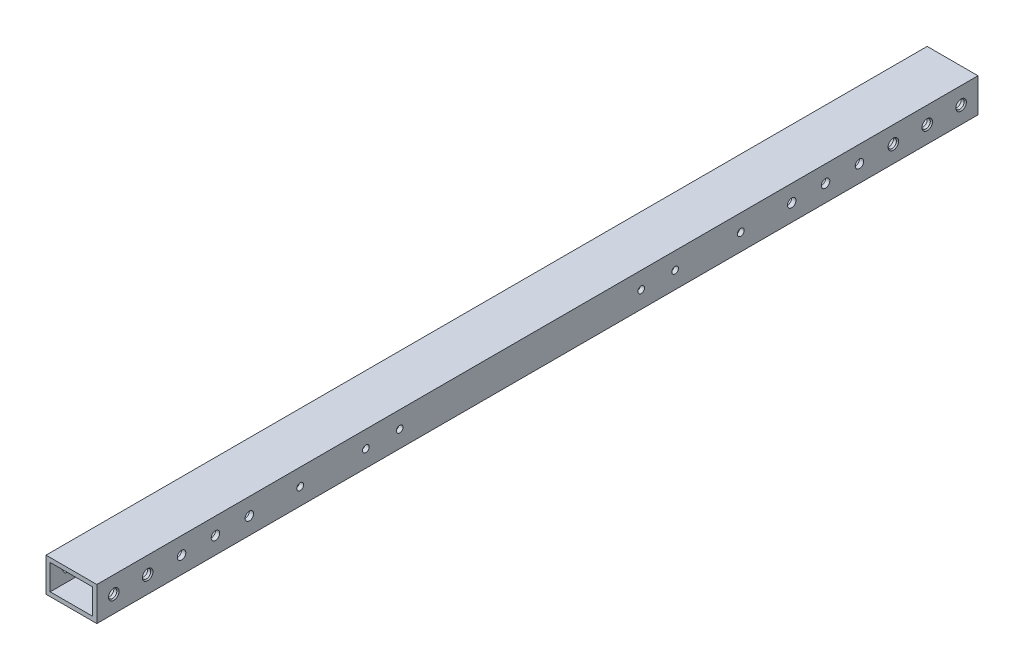
SolidWorks part; units mm, degrees
ref_plane "Front Plane" through (0, 0, 0) normal (0, 0, 1) x (1, 0, 0)
ref_plane "Top Plane" through (0, 0, 0) normal (0, 1, 0) x (1, 0, 0)
ref_plane "Right Plane" through (0, 0, 0) normal (1, 0, 0) x (0, 0, -1)
sketch "Sketch1" plane through (0, 0, 0) normal (0, 0, 1) x (1, 0, 0)
  line L0 (-15.875, 9.525) -> (15.875, 9.525)
  line L2 (-19.05, 12.7) -> (19.05, 12.7)
  line L3 (-19.05, 12.7) -> (-19.05, -12.7)
  line L4 (-19.05, -12.7) -> (19.05, -12.7)
  line L5 (19.05, 12.7) -> (19.05, -12.7)
  line L10 (15.875, 9.525) -> (15.875, -9.525)
  line L11 (-15.875, -9.525) -> (15.875, -9.525)
  line L12 (-15.875, 9.525) -> (-15.875, -9.525)
  point P12 (0, 12.7)
  point P14 (19.05, 0)
  dimension "Wall Thickness" = 3.175
  dimension "Outside Width" = 38.1
  dimension "Outside Height" = 25.4
  dimension "Inside Height" = 19.05
  dimension "Inside Width" = 31.75
sketch "Sketch2" plane through (0, 0, 0) normal (1, 0, 0) x (0, 0, -1)
  line L0 (330.2, 0) -> (-330.2, 0)
  point P4 (0, 0)
  point P7 (-330.2, 0)
  point P10 (330.2, 0)
  dimension "Length" = 660.4
sketch "Sketch3" plane through (0, 0, 0) normal (0, 0, 1) x (1, 0, 0)
  line L21 (19.05, 12.7) -> (-19.05, 12.7)
  line L22 (19.05, -12.7) -> (19.05, 12.7)
  line L23 (-19.05, -12.7) -> (19.05, -12.7)
  line L24 (-19.05, 12.7) -> (-19.05, -12.7)
  line L25 (19.05, 12.7) -> (-19.05, 12.7)
  line L26 (19.05, -12.7) -> (19.05, 12.7)
  line L27 (-19.05, -12.7) -> (19.05, -12.7)
  line L28 (-19.05, 12.7) -> (-19.05, -12.7)
  line L29 (15.875, 9.525) -> (-15.875, 9.525)
  line L30 (15.875, -9.525) -> (15.875, 9.525)
  line L31 (-15.875, -9.525) -> (15.875, -9.525)
  line L32 (-15.875, 9.525) -> (-15.875, -9.525)
  line L33 (15.875, 9.525) -> (-15.875, 9.525)
  line L34 (15.875, -9.525) -> (15.875, 9.525)
  line L35 (-15.875, -9.525) -> (15.875, -9.525)
  line L36 (-15.875, 9.525) -> (-15.875, -9.525)
  dimension "D1" = 0
  dimension "D2" = 0
extrude "Boss-Extrude1" add sketch "Sketch3" along normal up to vertex (330.2 mm away) and the other way up to vertex (330.2 mm away) up to point (0, 0, 330.2) other way up to point (0, 0, -330.2)
sketch "Drawing Reference" plane through (0, 0, 0) normal (1, 0, 0) x (0, 0, -1)
  line L0 (-330.2, 0) -> (330.2, 0) construction
  line L1 (0, -12.7) -> (0, 12.7) construction
  line L2 (-330.2, -12.7) -> (330.2, -12.7) construction
  line L5 (-330.2, 12.7) -> (330.2, 12.7) construction
  point P7 (-302.768, 0)
  point P8 (302.768, 0)
  dimension "D1" = 27.432
sketch "Sketch4" plane through (-19.05, 0, 0) normal (-1, 0, 0) x (0, 0, 1)
  line L0 (-330.2, 0) -> (-317.5574, 0)
  line L1 (-330.2, 12.7) -> (-330.2, -12.7) construction
  line L2 (-317.5574, 0) -> (-292.1574, 0)
  line L3 (-292.1574, 0) -> (-266.7574, 0)
  line L4 (-266.7574, 0) -> (-241.3574, 0)
  line L5 (-241.3574, 0) -> (-215.9574, 0)
  line L6 (-215.9574, 0) -> (-190.5574, 0)
  line L7 (330.2, 0) -> (317.5, 0)
  line L8 (330.2, 12.7) -> (330.2, -12.7) construction
  line L9 (317.5, 0) -> (292.1, 0)
  line L10 (292.1, 0) -> (266.7, 0)
  line L11 (266.7, 0) -> (241.3, 0)
  line L12 (241.3, 0) -> (215.9, 0)
hole_wizard "1/4 (0.25) Diameter Hole2" positions "Sketch7" profile "Sketch8" hole size "1/4" standard "ANSI Inch" end condition through all
sketch "Sketch7" plane through (-19.05, 0, 0) normal (-1, 0, 0) x (0, 0, 1)
  point P0 (-317.5574, 0)
  point P3 (-292.1574, 0)
  point P7 (317.5, 0)
  point P11 (-266.7574, 0)
  point P14 (292.1, 0)
sketch "Sketch8" plane through (-19.05, 0, -317.5574) normal (0, 1, 0) x (0, 0, 1)
  line L0 (0, 0) -> (0, 38.1)
  line L1 (0, 38.1) -> (3.9624, 38.1)
  line L2 (3.175, 37.1942) -> (3.175, 0)
  line L5 (3.175, 0) -> (0, 0)
  line L7 (3.9624, 38.1) -> (3.175, 37.1942)
  line L8 (-3.9624, 38.1) -> (-3.175, 37.1942) construction
  line L11 (0, -6.35) -> (0, 107.95) construction
  dimension "Thru Hole Dia." = 6.35
  dimension "Thru Hole Depth" = 38.1
  dimension "Far C'Sink Dia." = 7.9248
  dimension "Far C'Sink Angle" = 82
hole_wizard "1/4 (0.25) Diameter Hole3" positions "Sketch9" profile "Sketch10" hole size "1/4" standard "ANSI Inch" end condition through all
sketch "Sketch9" plane through (19.05, 0, 0) normal (1, 0, 0) x (0, 0, -1)
  point P0 (-266.7, 0)
  point P3 (-241.3, 0)
  point P6 (-215.9, 0)
  point P9 (241.3574, 0)
  point P12 (215.9574, 0)
  point P15 (190.5574, 0)
sketch "Sketch10" plane through (19.05, 0, 266.7) normal (0, 1, 0) x (0, 0, -1)
  line L0 (0, 0) -> (0, 38.1)
  line L1 (0, 38.1) -> (3.175, 38.1)
  line L2 (3.175, 38.1) -> (3.175, 0)
  line L5 (3.175, 0) -> (0, 0)
  line L11 (0, -6.35) -> (0, 107.95) construction
  dimension "Thru Hole Dia." = 6.35
  dimension "Thru Hole Depth" = 38.1
hole_wizard "13/64 (0.20313) Diameter Hole1" positions "Sketch11" profile "Sketch12" hole size "13/64" standard "ANSI Inch" end condition through all
sketch "Sketch11" plane through (19.05, 0, 0) normal (1, 0, 0) x (0, 0, -1)
  point P0 (152.4, 0)
  point P3 (-177.8, 0)
sketch "Sketch12" plane through (19.05, 0, -152.4) normal (0, 1, 0) x (0, 0, -1)
  line L0 (0, 0) -> (0, 38.1)
  line L1 (0, 38.1) -> (2.5798, 38.1)
  line L2 (2.5798, 38.1) -> (2.5798, 0)
  line L5 (2.5798, 0) -> (0, 0)
  line L11 (0, -6.35) -> (0, 107.95) construction
  dimension "Thru Hole Dia." = 5.1595
  dimension "Thru Hole Depth" = 38.1
sketch "Sketch13" plane through (19.05, 0, 0) normal (1, 0, 0) x (0, 0, -1)
  line L0 (-103.1875, 0) -> (-128.5875, 0)
  line L1 (77.7875, 0) -> (103.1875, 0)
hole_wizard "#10 Clearance Hole1" positions "Sketch14" profile "Sketch15" hole size "#10" standard "ANSI Inch" end condition through all
sketch "Sketch14" plane through (19.05, 0, 0) normal (1, 0, 0) x (0, 0, -1)
  point P0 (-128.5875, 0)
  point P3 (-103.1875, 0)
  point P7 (77.7875, 0)
  point P10 (103.1875, 0)
sketch "Sketch15" plane through (19.05, 0, 128.5875) normal (0, 1, 0) x (0, 0, -1)
  line L0 (0, 0) -> (0, 38.1)
  line L1 (0, 38.1) -> (2.4892, 38.1)
  line L2 (2.4892, 38.1) -> (2.4892, 0)
  line L5 (2.4892, 0) -> (0, 0)
  line L11 (0, -6.35) -> (0, 107.95) construction
  dimension "Thru Hole Dia." = 4.9784
  dimension "Thru Hole Depth" = 38.1
equation "\"D1@Drawing Reference\"=\"Outside Width@Sketch1\" * 0.72"
